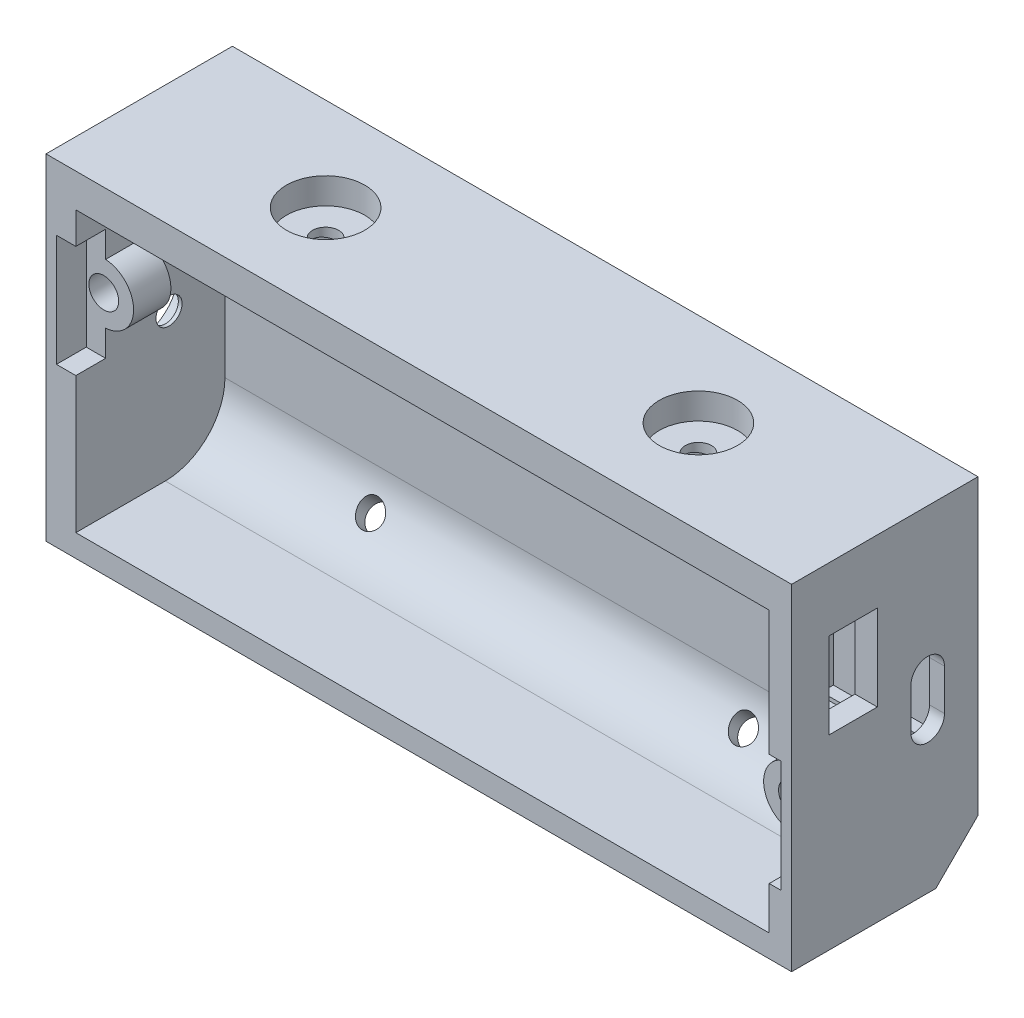
SolidWorks part; units mm, degrees
ref_plane "Plano frontal" through (0, 0, 0) normal (0, 0, 1) x (1, 0, 0)
ref_plane "Plano superior" through (0, 0, 0) normal (0, 1, 0) x (1, 0, 0)
ref_plane "Plano direito" through (0, 0, 0) normal (1, 0, 0) x (0, 0, -1)
sketch "Esboço1" plane through (0, 0, 0) normal (0, 0, 1) x (1, 0, 0)
  line L0 (-46, 18) -> (47, 18)
  line L1 (-50, 22.5) -> (50, 22.5)
  line L2 (-50, 22.5) -> (-50, -22.5)
  line L3 (-50, -22.5) -> (50, -22.5)
  line L4 (50, 22.5) -> (50, -22.5)
  line L5 (-50, 22.5) -> (50, -22.5) construction
  line L6 (-50, -22.5) -> (50, 22.5) construction
  line L7 (47, 18) -> (47, -19.5)
  line L8 (-46, -19.5) -> (47, -19.5)
  line L9 (-46, 18) -> (-46, -19.5)
  point P0 (0, 0)
  dimension "D2" = 45
  dimension "D3" = 100
  dimension "D4" = 4.5
  dimension "D1" = 4
  dimension "D5" = 3
  dimension "D6" = 3
extrude "Ressalto-extrusão1" add sketch "Esboço1" along normal blind 25 contours L0 L7 L8 L9 | L2 L1 L4 L3
extrude "Ressalto-extrusão2" add sketch "Esboço1<3>" along normal blind 5 contours L0 L9 L8 L7 region at (0.5, -0.75, 0)
sketch "Esboço1<3>" plane through (0, 0, 0) normal (0, 0, 1) x (1, 0, 0) same geometry as "Esboço1"
sketch "Esboço2" plane through (0, 22.5, 0) normal (0, -1, 0) x (1, 0, 0)
  line L0 (-50, 25) -> (-50, 0) construction
  line L1 (-50, 12.5) -> (50, 12.5) construction
  line L2 (50, 25) -> (50, 0) construction
  line L3 (0, 0) -> (0, 25) construction
  line L4 (-50, 0) -> (50, 0) construction
  line L5 (-50, 25) -> (50, 25) construction
  circle A0 centre (-25, 12.5) radius 5.25
  circle A2 centre (25, 12.5) radius 5.25
  circle A3 centre (-25, 12.5) radius 1.75
  circle A5 centre (25, 12.5) radius 1.75
  dimension "D1" = 10.5
  dimension "D5" = 3.5
  dimension "D2" = 50
  dimension "D3" = 25
extrude "Corte-extrusão1" cut sketch "Esboço2" along normal blind 3.5
sketch "Esboço14" plane through (-50, 0, 0) normal (-1, 0, 0) x (0, 0, 1)
  line L0 (0, 0) -> (25, 0) construction
  line L1 (25, 22.5) -> (25, -22.5) construction
  circle A0 centre (12.5, 0) radius 5.25
  circle A2 centre (12.5, 0) radius 1.75
  point P5 (12.5, 0)
  point P10 (12.5, 0)
  dimension "D1" = 10.5
  dimension "D2" = 3.5
extrude "Corte-extrusão17" cut sketch "Esboço14" against normal blind 3.5
sketch "Esboço4" plane through (0, 0, 0) normal (0, 0, -1) x (-1, 0, 0)
  line L0 (-50, 0) -> (50, 0) construction
  line L1 (-50, 22.5) -> (-50, -22.5) construction
  line L2 (50, 22.5) -> (50, -22.5) construction
  line L3 (0, 0) -> (0, 15.4115) construction
  circle A1 centre (-25, 0) radius 5.15
  circle A2 centre (25, 0) radius 5.15
  circle A3 centre (-25, 0) radius 1.75
  circle A5 centre (25, 0) radius 1.75
  dimension "D2" = 10.3
  dimension "D3" = 3.5
  dimension "D1" = 25
extrude "Corte-extrusão2" cut sketch "Esboço4" against normal blind 3.5
sketch "Esboço5" plane through (-50, 0, 0) normal (-1, 0, 0) x (0, 0, 1)
  line L1 (0, -16.8431) -> (5.6569, -22.5)
  line L2 (0, 22.5) -> (0, -22.5) construction
  line L9 (25, -22.5) -> (0, -22.5) construction
  line L10 (5.6569, -22.5) -> (0, -22.5)
  line L11 (0, -22.5) -> (0, -16.8431)
  dimension "D1" = 8
extrude "Corte-extrusão3" cut sketch "Esboço5" against normal through all
fillet "Filete1" radius 8 2 edges at (0.5, 18, 5) (0.5, -19.5, 5)
sketch "Esboço6" plane through (0, 8.4216, -25.2647) normal (0, 0.7071, 0.7071) x (1, 0, 0)
  line L0 (-50, -43.7297) -> (-50, -35.7297) construction
  line L1 (-31.25, -36.4797) -> (-18.75, -36.4797)
  line L2 (-31.25, -36.4797) -> (-31.25, -42.9797)
  line L3 (-31.25, -42.9797) -> (-18.75, -42.9797)
  line L4 (-18.75, -36.4797) -> (-18.75, -42.9797)
  line L5 (-31.25, -36.4797) -> (-18.75, -42.9797) construction
  line L6 (-31.25, -42.9797) -> (-18.75, -36.4797) construction
  line L7 (0, -23.8198) -> (0, 36.7394) construction
  line L8 (31.25, -42.9797) -> (18.75, -36.4797) construction
  line L9 (31.25, -36.4797) -> (18.75, -42.9797) construction
  line L10 (18.75, -36.4797) -> (18.75, -42.9797)
  line L11 (31.25, -42.9797) -> (18.75, -42.9797)
  line L12 (31.25, -36.4797) -> (31.25, -42.9797)
  line L13 (31.25, -36.4797) -> (18.75, -36.4797)
  circle A0 centre (25, -39.7297) radius 1.75
  circle A1 centre (-25, -39.7297) radius 1.75
  point P0 (-25, -39.7297)
  point P5 (-50, -39.7297)
  point P8 (-50, -39.7297)
  point P18 (25, -39.7297)
  dimension "D4" = 3.5
  dimension "D1" = 12.5
  dimension "D2" = 6.5
  dimension "D3" = 50
extrude "Corte-extrusão4" cut sketch "Esboço6" along normal blind 3.2 contours L13 L12 L11 L10 A0 | L1 L4 L3 L2 A1 region at (-25, -17.4731, 0.63) region at (25, -17.4731, 0.63)
extrude "Corte-extrusão5" cut sketch "Esboço4<2>" against normal through all contours A3 | A5
sketch "Esboço4<2>" plane through (0, 0, 0) normal (0, 0, -1) x (-1, 0, 0) same geometry as "Esboço4"
extrude "Corte-extrusão6" cut sketch "Esboço2<2>" along normal up to next contours A3 | A5
sketch "Esboço2<2>" plane through (0, 22.5, 0) normal (0, -1, 0) x (1, 0, 0) same geometry as "Esboço2"
extrude "Corte-extrusão8" cut sketch "Esboço6<2>" along normal through all contours A0 | A1
sketch "Esboço6<2>" plane through (0, 8.4216, -25.2647) normal (0, 0.7071, 0.7071) x (1, 0, 0) same geometry as "Esboço6"
sketch "Esboço8" plane through (0, 0, 25) normal (0, 0, 1) x (1, 0, 0)
  line L0 (50, 22.5) -> (50, -22.5) construction
  line L1 (32, -10) -> (48, -10)
  line L2 (32, -10) -> (32, 6)
  line L3 (32, 6) -> (48, 6)
  line L4 (48, -10) -> (48, 6)
  line L5 (32, -10) -> (48, 6) construction
  line L6 (32, 6) -> (48, -10) construction
  point P0 (40, -2)
  point P5 (40, 2.9052)
  dimension "D1" = 16
  dimension "D2" = 16
  dimension "D3" = 2
  dimension "D4" = 2
extrude "DIY-charger" cut sketch "Esboço8" against normal blind 1.5 and the other way blind 6 from surface starting at face at (26.75, 0, 5)
sketch "Esboço9" plane through (48, 0, 0) normal (-1, 0, 0) x (0, 0, 1)
  line L0 (6.75, 2.75) -> (6.75, -2.75) construction
  line L1 (9, 2.75) -> (9, -2.75)
  line L2 (4.5, 2.75) -> (4.5, -2.75)
  line L3 (3.5, 6) -> (3.5, -10) construction
  line L4 (3.5, -10) -> (3.5, 6) construction
  arc A0 (9, 2.75) -> (4.5, 2.75) centre (6.75, 2.75) ccw
  arc A1 (4.5, -2.75) -> (9, -2.75) centre (6.75, -2.75) ccw
  point P2 (6.75, 0)
  point P7 (3.5, -2)
  dimension "D1" = 10
  dimension "D2" = 2.25
  dimension "D3" = 1
  dimension "D4" = 2
extrude "Corte-extrusão11" cut sketch "Esboço9" against normal through all
sketch "Esboço10" plane through (0, 0, 3.5) normal (0, 0, 1) x (1, 0, 0)
  line L0 (47.5, -8) -> (47.5, 4)
  line L1 (40.5, 5.5) -> (32.5, 5.5)
  line L2 (32.5, 5.5) -> (32.5, -9.5)
  line L3 (32.5, -9.5) -> (40.5, -9.5)
  line L4 (48, -10) -> (48, 6)
  line L5 (48, 6) -> (32, 6)
  line L6 (32, 6) -> (32, -10)
  line L7 (32, -10) -> (48, -10)
  line L8 (48, -10) -> (48, 6) construction
  line L9 (48, 6) -> (32, 6) construction
  line L10 (32, 6) -> (32, -10) construction
  line L11 (32, -10) -> (48, -10) construction
  line L12 (40.5, 5.5) -> (40.5, 4)
  line L13 (40.5, 4) -> (47.5, 4)
  line L14 (40.5, -9.5) -> (40.5, -8)
  line L15 (40.5, -8) -> (47.5, -8)
  line L16 (47.5, 5.5) -> (32.5, 5.5) construction
  line L17 (47.5, -9.5) -> (47.5, 5.5) construction
  line L18 (32.5, -9.5) -> (47.5, -9.5) construction
  circle A0 centre (30.9, 3) radius 1
  circle A1 centre (30.9, 3) radius 2 construction
  circle A2 centre (25, 0) radius 1.75 construction
  dimension "D5" = 2
  dimension "D6" = 4
  dimension "D7" = 3
  dimension "D8" = 0.1
  dimension "D3" = 2
  dimension "D4" = 7
  dimension "D1" = 0
  dimension "D2" = 0.5
extrude "Corte-extrusão12" cut sketch "Esboço10" against normal blind 1.6 and the other way blind 2
sketch "Esboço12" plane through (47, 0, 0) normal (-1, 0, 0) x (0, 0, 1)
  line L0 (25, 18) -> (25, -19.5) construction
  line L1 (20, 14) -> (13.5, 14)
  line L2 (20, 14) -> (20, 2.5)
  line L3 (20, 2.5) -> (13.5, 2.5)
  line L4 (13.5, 14) -> (13.5, 2.5)
  line L5 (20, 14) -> (13.5, 2.5) construction
  line L6 (20, 2.5) -> (13.5, 14) construction
  line L7 (25, 18) -> (13, 18) construction
  line L8 (20.5, 18.5) -> (20.5, -2)
  line L9 (20.5, -2) -> (13, -2) construction
  line L10 (13, 18.5) -> (13, -2)
  line L11 (20.5, 18.5) -> (13, 18.5)
  line L12 (16.75, 8.25) -> (22.5311, 8.25) construction
  circle A0 centre (16.75, 16.5) radius 1
  circle A1 centre (16.75, 0) radius 1
  point P0 (16.75, 8.25)
  point P19 (0, 0)
  dimension "D9" = 2
  dimension "D1" = 11.5
  dimension "D2" = 6.5
  dimension "D3" = 5
  dimension "D4" = 4
  dimension "D5" = 0.5
  dimension "D6" = 0.5
  dimension "D7" = 4.5
  dimension "D8" = 4.5
  dimension "D10" = 16.5
extrude "Corte-extrusão14" cut sketch "Esboço12" against normal through all contours L2 L1 L4 L3
extrude "Corte-extrusão15" cut sketch "Esboço12<3>" against normal offset from surface 1.5 and the other way blind 3 contours A1 | A0 region at (47, 16.5, 16.75) region at (47, 0, 16.75) up to face at (50, 0, 6.75)
sketch "Esboço12<3>" plane through (47, 0, 0) normal (-1, 0, 0) x (0, 0, 1) same geometry as "Esboço12"
sketch "Esboço13" plane through (0, 0, 25) normal (0, 0, 1) x (1, 0, 0)
  line L0 (50, 22.5) -> (50, -22.5) construction
  line L1 (-50, -22.5) -> (50, -22.5) construction
  line L2 (0, 0) -> (4.9647, 36.739) construction
  line L3 (-50, 22.5) -> (-50, -22.5) construction
  circle A0 centre (46.25, -6.25) radius 2
  circle A1 centre (46.25, -6.25) radius 4
  circle A2 centre (-46.25, 6.25) radius 4
  circle A3 centre (-46.25, 6.25) radius 2
  line M9 (-46, -19.5) -> (-46, 18)
  line M11 (47, 18) -> (47, -19.5)
  dimension "D1" = 8
  dimension "D2" = 4
  dimension "D3" = 3.75
  dimension "D4" = 16.25
  dimension "D5" = 3.75
extrude "Ressalto-extrusão4" add sketch "Esboço13" against normal blind 5 from offset 4 contours A3 A2 M9 | A1 A0 M11 region at (44.157, -6.25, 25) region at (-44.1653, 6.25, 25) offset against normal yes
extrude "Corte-extrusão16" cut sketch "Esboço13<3>" against normal blind 10 contours A3 | A0
sketch "Esboço13<3>" plane through (0, 0, 25) normal (0, 0, 1) x (1, 0, 0) same geometry as "Esboço13"
extrude "Corte-extrusão18" cut sketch "Esboço14<2>" against normal up to next contours A2 region at (-50, 0, 12.5)
sketch "Esboço14<2>" plane through (-50, 0, 0) normal (-1, 0, 0) x (0, 0, 1) same geometry as "Esboço14"
sketch "Esboço16" plane through (0, 0, 25) normal (0, 0, 1) x (1, 0, 0)
  line L0 (50, 22.5) -> (50, -22.5) construction
  line L1 (-43.9, 13.75) -> (-48.6, 13.75)
  line L2 (-43.9, 13.75) -> (-43.9, -1.25)
  line L3 (-43.9, -1.25) -> (-48.6, -1.25)
  line L4 (-48.6, 13.75) -> (-48.6, -1.25)
  line L5 (-43.9, 13.75) -> (-48.6, -1.25) construction
  line L6 (-43.9, -1.25) -> (-48.6, 13.75) construction
  line L7 (43.9, 1.25) -> (48.6, 1.25)
  line L8 (43.9, 1.25) -> (43.9, -13.75)
  line L9 (43.9, -13.75) -> (48.6, -13.75)
  line L10 (48.6, 1.25) -> (48.6, -13.75)
  line L11 (43.9, 1.25) -> (48.6, -13.75) construction
  line L12 (43.9, -13.75) -> (48.6, 1.25) construction
  point P0 (-46.25, 6.25)
  point P6 (46.25, -6.25)
  dimension "D1" = 1.4
  dimension "D2" = 15
extrude "Corte-extrusão19" cut sketch "Esboço16" against normal up to surface (4 mm away) up to face at (-44.625, 6.25, 21)
equation "\"D6@Esboço12\"=\"D5@Esboço12\""
equation "\"D8@Esboço12\"=\"D7@Esboço12\""
